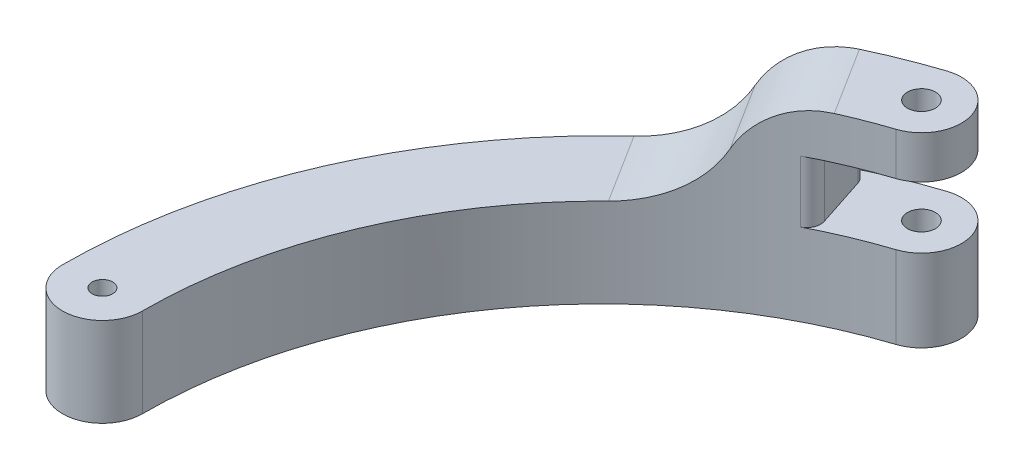
SolidWorks part; units mm, degrees
material "ABS"
ref_plane "Front Plane" through (0, 0, 0) normal (0, 0, 1) x (1, 0, 0)
ref_plane "Top Plane" through (0, 0, 0) normal (0, 1, 0) x (1, 0, 0)
ref_plane "Right Plane" through (0, 0, 0) normal (1, 0, 0) x (0, 0, -1)
sketch "Sketch1" plane through (0, 0, 0) normal (0, 1, 0) x (1, 0, 0)
  arc A2 (-33.5905, 0) -> (-10.4454, 31.9251) centre (0, 0) cw
  arc A3 (-39.4345, 0) -> (-12.2627, 37.4794) centre (0, 0) cw
  arc A4 (-10.4454, 31.9251) -> (-12.2627, 37.4794) centre (-11.3541, 34.7023) ccw
  arc A5 (-33.5905, 0) -> (-39.4345, 0) centre (-36.5125, 0) cw
  circle A6 centre (-36.5125, 0) radius 0.75
  circle A7 centre (-11.3541, 34.7023) radius 1.025
  dimension "D3" = 1.5
  dimension "D4" = 2.05
  dimension "D1" = 42.8625
  dimension "D2" = 36.5125
extrude "Boss-Extrude1" add sketch "Sketch1" along normal blind 6.51
sketch "Esquisse1" plane through (0, 6.51, 0) normal (0, 1, 0) x (1, 0, 0)
  line L0 (-17.9042, 28.4212) -> (-21.0191, 33.3658)
  arc A0 (-10.4454, 31.9251) -> (-33.5905, 0) centre (0, 0) ccw construction
  arc A1 (-12.2627, 37.4794) -> (-39.4345, 0) centre (0, 0) ccw construction
  arc A2 (-10.4454, 31.9251) -> (-12.2627, 37.4794) centre (-11.3541, 34.7023) ccw construction
  arc A3 (-10.4454, 31.9251) -> (-17.9042, 28.4212) centre (0, 0) ccw
  arc A4 (-12.2627, 37.4794) -> (-21.0191, 33.3658) centre (0, 0) ccw
  arc A5 (-10.4454, 31.9251) -> (-12.2627, 37.4794) centre (-11.3541, 34.7023) ccw
  dimension "D1" = 8.89
extrude "Boss.-Extru.1" add sketch "Esquisse1" along normal blind 7.112
fillet "Congé1" radius 7.112 1 edges at (-19.4616, 6.51, -30.8935)
fillet "Congé2" radius 6.35 1 edges at (-19.4616, 13.622, -30.8935)
ref_plane "Plan1" through (-12.2627, 0, -37.4794) normal (-0.9504, 0, 0.311) x (0.311, 0, 0.9504)
sketch "Esquisse3" plane through (-12.2627, 0, -37.4794) normal (-0.9504, 0, 0.311) x (0.311, 0, 0.9504)
  line L1 (-5.9298, 10.5) -> (8.1531, 10.5)
  line L2 (-5.9298, 10.5) -> (-5.9298, 6)
  line L3 (-5.9298, 6) -> (8.1531, 6)
  line L4 (8.1531, 10.5) -> (8.1531, 6)
  line L6 (0, 0) -> (27.1718, 0) construction
  dimension "D1" = 4.5
  dimension "D2" = 6
extrude "Enlèv. mat.-Extru.1" cut sketch "Esquisse3" against normal mid plane 8.89
sketch "Esquisse4" plane through (0, 0, 0) normal (0, -1, 0) x (1, 0, 0)
  circle A1 centre (-11.3541, -34.7023) radius 1.025
  circle A2 centre (-11.3541, -34.7023) radius 1.025 construction
extrude "Enlèv. mat.-Extru.2" cut sketch "Esquisse4" against normal through all
fillet "Congé3" radius 1.016 2 edges at (-14.5782, 8.25, -30.2622) (-16.4092, 8.25, -35.8583)
fillet "Congé4" [suppressed] radius 1.016
